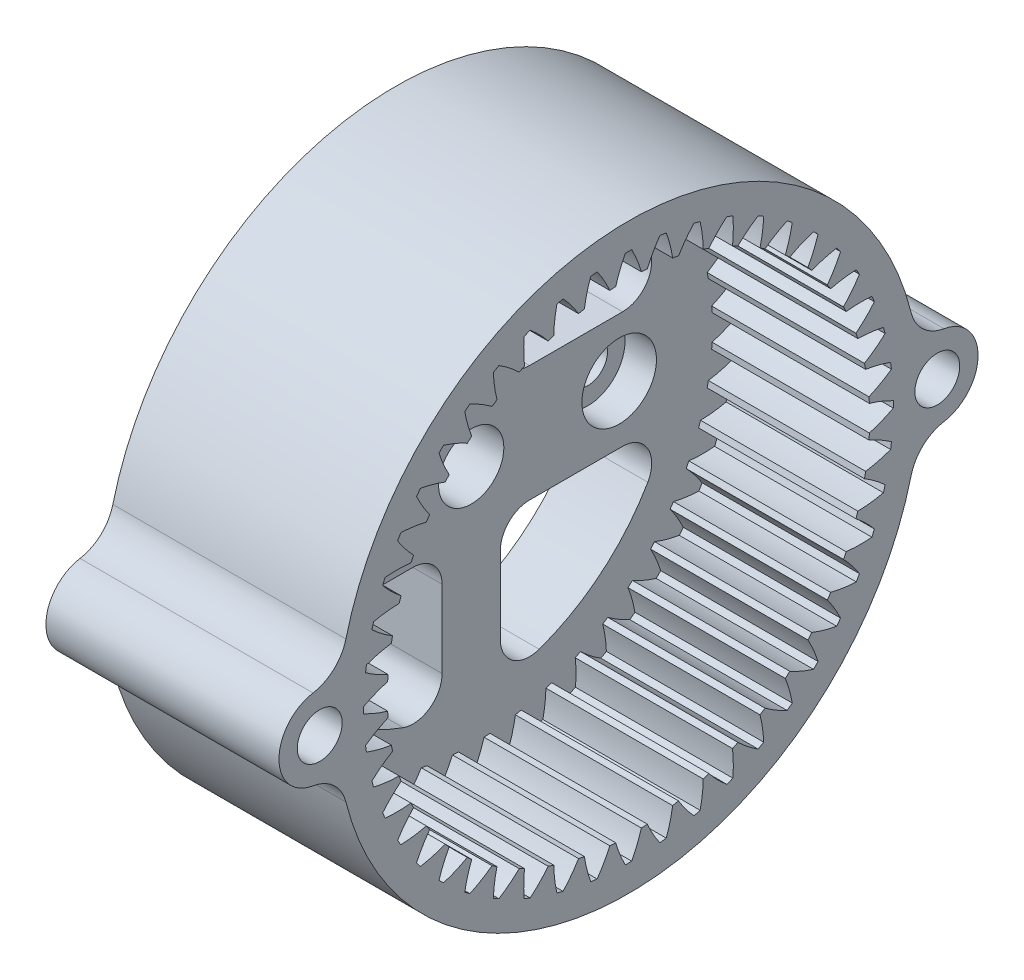
SolidWorks part; units mm, degrees
other "Markup1"
sketch "Sketch6" plane through (-6.5, 25, -30) normal (0, 1, 0) x (1, 0, 0)
ref_plane "Plane1" through (0, 0, 0) normal (0, 0, 1) x (1, 0, 0)
ref_plane "Plane2" through (0, 0, 0) normal (0, 1, 0) x (1, 0, 0)
ref_plane "Plane3" through (0, 0, 0) normal (1, 0, 0) x (0, 0, -1)
other "Configuration Table"
sketch "HoldingSke" plane through (0, 0, 0) normal (0, 1, 0) x (1, 0, 0)
  line L0 (0, 0) -> (0.7435, -0.8257)
  line L1 (-15, 0) -> (100, 0) construction
  line L2 (0, 0) -> (-2.1039, 2.3779)
  line L3 (0, 0) -> (-11.863, 4.5341)
  line L4 (0, 0) -> (5.7786, 6.4178)
  line L5 (0, 0) -> (-23.7986, -8.8762)
  line L6 (0, 0) -> (-10.5278, -7.1032)
  line L7 (-2.1039, 2.3779) -> (3.3635, 27.1825)
  line L8 (-76.2, 3.2779) -> (-54.61, 3.2779)
  line L9 (-71.009, 38.7566) -> (-53.1078, 45.2721)
  line L10 (-76.2, 71.12) -> (104.1128, 71.12)
  line L11 (0, 0) -> (-12, 0)
  line L12 (-76.2, 101.6) -> (-76.166, 101.6)
  line L13 (24.9733, 27.94) -> (52.9518, 28.4284)
  line L14 (24.9733, 27.94) -> (24.9743, 27.94)
  line L15 (24.9733, 27.94) -> (100.4006, 29.5858)
  circle A0 centre (0, 0) radius 25
  circle A1 centre (0, 0) radius 12.7
  circle A2 centre (0, 0) radius 12.7
  dimension "MHD" = 25.4
  dimension "Hub_dia" = 25.4
  dimension "Diameter" = 50
  dimension "Num_teeth" = 48
  dimension "Pitch" = 1.1111
  dimension "Overall_len" = 25.4
  dimension "Show_teeth" = 48
  dimension "Thickness" = 12.7
  dimension "OAL" = 25.4001
  dimension "T_dim" = 21.59
  dimension "Ap" = 20
  dimension "H" = 19.05
  dimension "Pitch_radius" = 180.3128
  dimension "Width" = 12
  dimension "Backlash" = 0.034
  dimension "Addendum_fac" = 1
  dimension "Dedendum_fac" = 1.25
  dimension "Clearance_fac" = 0.25
  dimension "Dedendum_add" = 0.001
  dimension "Module" = 0.9
sketch "BasProSke" plane through (0, 0, 0) normal (0, 1, 0) x (1, 0, 0)
  line L0 (-10, 0) -> (60, 0) construction
  line L1 (0, 20.7) -> (0, 25)
  line L2 (0, 20.7) -> (13.5, 20.7)
  line L3 (13.5, 20.7) -> (13.5, 25)
  line L4 (13.5, 25) -> (0, 25)
  dimension "Diameter" = 50
  dimension "Thickness" = 13.5
  dimension "Inside_diameter" = 41.4
revolve "Base-Revolve" add sketch "BasProSke" angle 360 about L0
sketch "TooCutSke" plane through (0, 0, 0) normal (1, 0, 0) x (0, 0, -1)
  line L3 (0.7917, 21.5855) -> (0.7917, 53.6633) construction
  line L4 (0, 0) -> (0, 59.563) construction
  line L5 (0, 0) -> (-4.4688, 68.1812) construction
  line L6 (-9.2845, 17.6983) -> (36.567, 20.7035) construction
  circle A0 centre (0, 0) radius 21.6 construction
  circle A1 centre (0, 0) radius 22.726 construction
  circle A2 centre (0, 0) radius 18.2676 construction
  circle A3 centre (0, 0) radius 20.6746 construction
  arc A4 (1.1058, 20.645) -> (0.2748, 22.7243) centre (-9.2845, 17.6983) ccw
  arc A5 (1.1058, 20.645) -> (-1.1058, 20.645) centre (0, 0) ccw
  arc A6 (0.2748, 22.7243) -> (-0.2748, 22.7243) centre (0, 0) ccw
  arc A7 (-0.2748, 22.7243) -> (-1.1058, 20.645) centre (9.2845, 17.6983) ccw
  dimension "Pitch_dia" = 43.2
  dimension "Base_dia" = 36.5352
  dimension "Root_dia" = 45.452
  dimension "Overcut_dia" = 41.3492
  dimension "Flank_rad" = 10.8
  dimension "Half_ang" = 3.75
  dimension "Half_CT" = 0.7917
extrude "ToothCut" cut sketch "TooCutSke" along normal through all
fillet "Breaks" [suppressed] radius 0.09
fillet "RootFillets" [suppressed] radius 0.226
pattern_circular "TeethCuts" count 48 every 7.5 about axis through (-10, 0, 0) along (1, 0, 0) of "RootFillets", "Breaks", "ToothCut"
sketch "Sketch1" plane through (0, 0, 0) normal (-1, 0, 0) x (0, 0, 1)
  line L0 (0, 22.726) -> (0, -22.726) construction
  circle A0 centre (0, 0) radius 25 construction
  circle A1 centre (0, 0) radius 25
  circle A2 centre (0, 0) radius 2.8
  circle A3 centre (-12.7, 0) radius 3.2
  arc A4 (-0.2748, -22.7243) -> (0.2748, -22.7243) centre (0, 0) ccw construction
  circle A5 centre (12.7, 0) radius 3.2
  point P11 (0, 0)
  dimension "D1" = 5.6
  dimension "D3" = 6.4
  dimension "D2" = 12.7
extrude "Boss-Extrude1" add sketch "Sketch1" along normal blind 2.7
sketch "Sketch2" plane through (-2.7, 0, 0) normal (-1, 0, 0) x (0, 0, 1)
  circle A0 centre (0, 0) radius 25 construction
  circle A1 centre (0, 0) radius 2.8 construction
  circle A2 centre (0, 0) radius 25
  circle A3 centre (0, 0) radius 2.8
  circle A4 centre (-12.7, 0) radius 1.7
  circle A5 centre (12.7, 0) radius 1.7
  dimension "D1" = 3.4
extrude "Boss-Extrude2" add sketch "Sketch2" along normal blind 3.8
sketch "Sketch4" plane through (13.5, 0, 0) normal (1, 0, 0) x (0, 0, -1)
  line L0 (0, 0) -> (26.5, 0) construction
  line L1 (0, 22.726) -> (0, -22.726) construction
  line L2 (-26.5, -3.5) -> (-24.7538, -3.5)
  line L3 (26.5, -3.5) -> (24.7538, -3.5)
  line L4 (26.5, 3.5) -> (24.7538, 3.5)
  line L5 (-26.5, 3.5) -> (-24.7538, 3.5)
  arc A0 (26.5, -3.5) -> (26.5, 3.5) centre (26.5, 0) ccw
  circle A1 centre (0, 0) radius 25 construction
  circle A2 centre (0, 0) radius 25 construction
  arc A4 (-0.2748, -22.7243) -> (0.2748, -22.7243) centre (0, 0) ccw construction
  arc A5 (24.7538, -3.5) -> (24.7538, 3.5) centre (0, 0) ccw
  arc A6 (-26.5, -3.5) -> (-26.5, 3.5) centre (-26.5, 0) cw
  arc A7 (-24.7538, -3.5) -> (-24.7538, 3.5) centre (0, 0) cw
  point P16 (0, 0)
  dimension "D1" = 7
  dimension "D2" = 26.5
extrude "Boss-Extrude3" add sketch "Sketch4" against normal up to surface (20 mm away) up to face at (-6.5, 0, -11)
sketch "Sketch5" plane through (13.5, 0, 0) normal (1, 0, 0) x (0, 0, -1)
  circle A0 centre (26.5, 0) radius 1.925
  arc A1 (26.5, -3.5) -> (26.5, 3.5) centre (26.5, 0) ccw construction
  circle A2 centre (-26.5, 0) radius 1.925
  arc A4 (-26.5, 3.5) -> (-26.5, -3.5) centre (-26.5, 0) ccw construction
  dimension "D1" = 3.85
extrude "Cut-Extrude2" cut sketch "Sketch5" against normal blind 5.5
fillet "Fillet2" radius 3.5 4 edges at (3.5, -3.5, 24.7538) (3.5, 3.5, -24.7538) (3.5, -3.5, -24.7538) (3.5, 3.5, 24.7538)
sketch "Sketch7" plane through (0, 0, 0) normal (1, 0, 0) x (0, 0, -1)
  line L0 (0, -22.726) -> (0, 22.726) construction
  line L1 (-22.726, 0) -> (22.726, 0) construction
  line L2 (-12.9904, -5) -> (-5, -5)
  line L3 (-2.5, -7.5) -> (-2.5, -14.1421)
  line L4 (12.9904, -5) -> (5, -5)
  line L5 (2.5, -7.5) -> (2.5, -14.1421)
  line L6 (12.9904, 5) -> (5, 5)
  line L7 (2.5, 7.5) -> (2.5, 14.1421)
  line L8 (-12.9904, 5) -> (-5, 5)
  line L9 (-2.5, 7.5) -> (-2.5, 14.1421)
  arc A0 (0.2748, 22.7243) -> (-0.2748, 22.7243) centre (0, 0) ccw construction
  arc A1 (22.7243, -0.2748) -> (22.7243, 0.2748) centre (0, 0) ccw construction
  arc A2 (-5.8333, -16.4992) -> (-15.1554, -8.75) centre (0, 0) cw
  arc A3 (-24.2552, -6.0568) -> (24.2552, -6.0568) centre (0, 0) ccw construction
  arc A4 (-5.8333, -16.4992) -> (-2.5, -14.1421) centre (-5, -14.1421) ccw
  arc A5 (-2.5, -7.5) -> (-5, -5) centre (-5, -7.5) ccw
  arc A6 (-12.9904, -5) -> (-15.1554, -8.75) centre (-12.9904, -7.5) ccw
  arc A7 (12.9904, -5) -> (15.1554, -8.75) centre (12.9904, -7.5) cw
  arc A8 (5.8333, -16.4992) -> (15.1554, -8.75) centre (0, 0) ccw
  arc A9 (5.8333, -16.4992) -> (2.5, -14.1421) centre (5, -14.1421) cw
  arc A10 (2.5, -7.5) -> (5, -5) centre (5, -7.5) cw
  arc A11 (2.5, 7.5) -> (5, 5) centre (5, 7.5) ccw
  arc A12 (5.8333, 16.4992) -> (2.5, 14.1421) centre (5, 14.1421) ccw
  arc A13 (5.8333, 16.4992) -> (15.1554, 8.75) centre (0, 0) cw
  arc A14 (12.9904, 5) -> (15.1554, 8.75) centre (12.9904, 7.5) ccw
  arc A15 (-12.9904, 5) -> (-15.1554, 8.75) centre (-12.9904, 7.5) cw
  arc A16 (-5.8333, 16.4992) -> (-15.1554, 8.75) centre (0, 0) ccw
  arc A17 (-5.8333, 16.4992) -> (-2.5, 14.1421) centre (-5, 14.1421) cw
  arc A18 (-2.5, 7.5) -> (-5, 5) centre (-5, 7.5) cw
  point P9 (0, 0)
  point P16 (0, 0)
  dimension "D3" = 7.5
  dimension "D4" = 2.5
  dimension "D1" = 2.5
  dimension "D2" = 5
extrude "Cut-Extrude3" cut sketch "Sketch7" against normal through all
equation "' \"Module@HoldingSke\" = 6.35"
equation "' \"Num_teeth@HoldingSke\" = 24"
equation "' \"Ap@HoldingSke\" =  14.5"
equation "' \"Ap@HoldingSke\" = 14.5"
equation "' \"Width@HoldingSke\" = 12"
equation "' \"Diameter@HoldingSke\" = 8 * 25.4"
equation "' \"Show_teeth@HoldingSke\" = 100"
equation "' \"Backlash@HoldingSke\" = 0.009 * 25.4"
equation "' \"Addendum_fac@HoldingSke\" = 1.0"
equation "' \"Dedendum_fac@HoldingSke\" = 1.25"
equation "' \"Dedendum_add@HoldingSke\" = 0.00005 * 25.4"
equation "' \"Clearance_fac@HoldingSke\" = 0.25"
equation "\"Pitch@HoldingSke\" = 1 / \"Module@HoldingSke\" "
equation "\"Overcut_dia@TooCutSke\" = (\"Num_teeth@HoldingSke\" - 2 * \"Addendum_fac@HoldingSke\") / \"Pitch@HoldingSke\" - 0.002 * 25.4"
equation "\"Pitch_dia@TooCutSke\" = \"Num_teeth@HoldingSke\" / \"Pitch@HoldingSke\""
equation "\"Base_dia@TooCutSke\" = \"Num_teeth@HoldingSke\" / \"Pitch@HoldingSke\" * cos((\"Ap@HoldingSke\"  * 3.14159265 / 180)) * 0.90"
equation "\"Root_dia@TooCutSke\" = \"Num_teeth@HoldingSke\"  / \"Pitch@HoldingSke\" + 2 *  \"Dedendum_fac@HoldingSke\"/ \"Pitch@HoldingSke\" + \"Dedendum_add@HoldingSke\" * 2"
equation "\"Half_ang@TooCutSke\" = 180 / \"Num_teeth@HoldingSke\""
equation "\"Half_CT@TooCutSke\" = \"Num_teeth@HoldingSke\" / \"Pitch@HoldingSke\" * sin((3.14159265 / 2 / \"Num_teeth@HoldingSke\")) / 2 + 10 * \"Backlash@HoldingSke\" / 4"
equation "\"Flank_rad@TooCutSke\" = \"Num_teeth@HoldingSke\" / \"Pitch@HoldingSke\" / 4"
equation "\"Radius@RootFillets\"= \"Clearance_fac@HoldingSke\" / \"Pitch@HoldingSke\" + \"Dedendum_add@HoldingSke\""
equation "\"Break_rad@Breaks\" = 0.02 / \"Pitch@HoldingSke\" * 5"
equation "\"Num_teeth@TeethCuts\" = int( \"Show_teeth@HoldingSke\" ) + 1"
equation "\"Num_teeth@TeethCuts\" = ((sgn( \"Num_teeth@TeethCuts\" - \"Num_teeth@HoldingSke\" )-1)*( \"Num_teeth@TeethCuts\" - \"Num_teeth@HoldingSke\" ))/-2+ \"Num_teeth@HoldingSke\""
equation "\"Num_teeth@TeethCuts\" = ((sgn( \"Num_teeth@TeethCuts\" - 2.0)+1)*( \"Num_teeth@TeethCuts\" - 2.0))/2 +2.0"
equation "\"Angle@TeethCuts\" = 360.0 / \"Num_teeth@HoldingSke\""
equation "\"Diameter@BasProSke\" = \"Num_teeth@HoldingSke\"  / \"Pitch@HoldingSke\" + 2 *  \"Dedendum_fac@HoldingSke\"/ \"Pitch@HoldingSke\" + \"Dedendum_add@HoldingSke\" * 2 + 0.002 * 25.4"
equation "\"Diameter@BasProSke\" = ((sgn( \"Diameter@BasProSke\"  - \"Diameter@HoldingSke\" )+1)*( \"Diameter@BasProSke\"  - \"Diameter@HoldingSke\" ))/2 + \"Diameter@HoldingSke\""
equation "\"Inside_diameter@BasProSke\" =  (\"Num_teeth@HoldingSke\" - 2 * \"Addendum_fac@HoldingSke\") / \"Pitch@HoldingSke\" "
